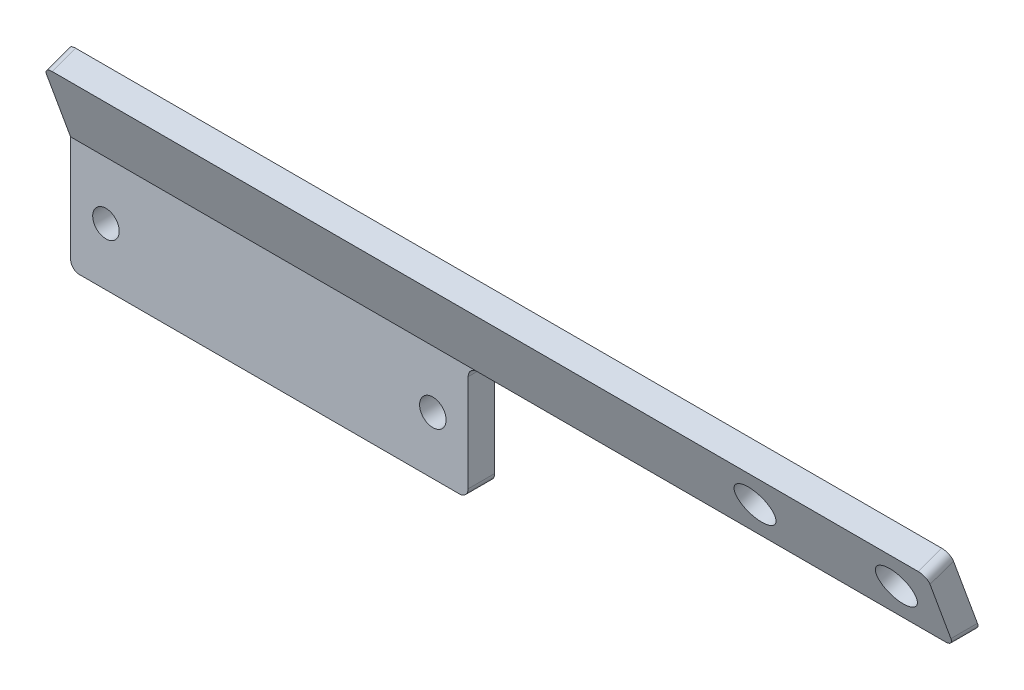
SolidWorks part; units mm, degrees
ref_plane "Plan de face" through (0, 0, 0) normal (0, 0, 1) x (1, 0, 0)
ref_plane "Plan de dessus" through (0, 0, 0) normal (0, 1, 0) x (1, 0, 0)
ref_plane "Plan de droite" through (0, 0, 0) normal (1, 0, 0) x (0, 0, -1)
sketch "Esquisse1" plane through (0, 0, 0) normal (0, 0, 1) x (1, 0, 0)
  line L1 (0, 0) -> (45, 0)
  line L2 (0, 0) -> (0, 13)
  line L3 (0, 13) -> (45, 13)
  line L4 (45, 0) -> (45, 13)
  dimension "D1" = 13
  dimension "D2" = 45
extrude "Boss.-Extru.1" add sketch "Esquisse1" along normal blind 3
ref_plane "Plan1" through (22.5, 0, 0) normal (-1, 0, 0) x (0, 0, 1)
sketch "Esquisse2" plane through (0, 0, 3) normal (0, 0, 1) x (1, 0, 0)
  line L0 (22.5, 1.65) -> (22.5, -1.65) construction
  line L1 (0, 0) -> (45, 0) construction
  circle A0 centre (41, 6.5) radius 1.5
  dimension "D2" = 3
  dimension "D1" = 18.5
  dimension "D3" = 6.5
extrude "Enlèv. mat.-Extru.1" cut sketch "Esquisse2" against normal through all
mirror "Symétrie1" about plane through (22.5, 0, 0) normal (-1, 0, 0) of "Enlèv. mat.-Extru.1"
ref_plane "Plan2" through (0, 0, 1.5) normal (0, 0, 1) x (1, 0, 0)
ref_axis "Axe1" through (22.5, 13.65, 1.5) along (0, -1, 0)
sketch "Esquisse8" plane through (0, 0, 0) normal (-1, 0, 0) x (0, 0, 1)
  line L0 (0, 13) -> (3.4202, 22.3969)
  line L1 (3.4202, 22.3969) -> (6.0693, 21.4327)
  line L2 (6.0693, 21.4327) -> (3, 13)
  line L4 (3, 13) -> (0, 13)
  line L5 (3, 13) -> (0, 13) construction
  line L6 (0, 0) -> (0, 50000) construction
  dimension "D1" = 10
  dimension "D2" = 20
extrude "Boss.-Extru.3" add sketch "Esquisse8" against normal blind 100
fillet "Congé1" radius 1 6 edges at (45, 0, 1.5) (0, 0, 1.5) (100, 13, 1.5) (100, 21.9148, 4.7447) (0, 21.9148, 4.7447)
sketch "Esquisse12" plane through (0, 0.5565, -1.5291) normal (0, -0.342, 0.9397) x (1, 0, 0)
  line L0 (100, 14.3062) -> (100, 21.216) construction
  line L1 (99, 13.2421) -> (46, 13.2421) construction
  circle A0 centre (95, 17.7421) radius 2.25
  dimension "D3" = 4.5
  dimension "D1" = 5
  dimension "D2" = 4.5
extrude "Enlèv. mat.-Extru.3" cut sketch "Esquisse12" against normal through all
pattern_linear "Répétition linéaire1" count 2 spacing 16 along (-1, 0, 0) of "Enlèv. mat.-Extru.3"
